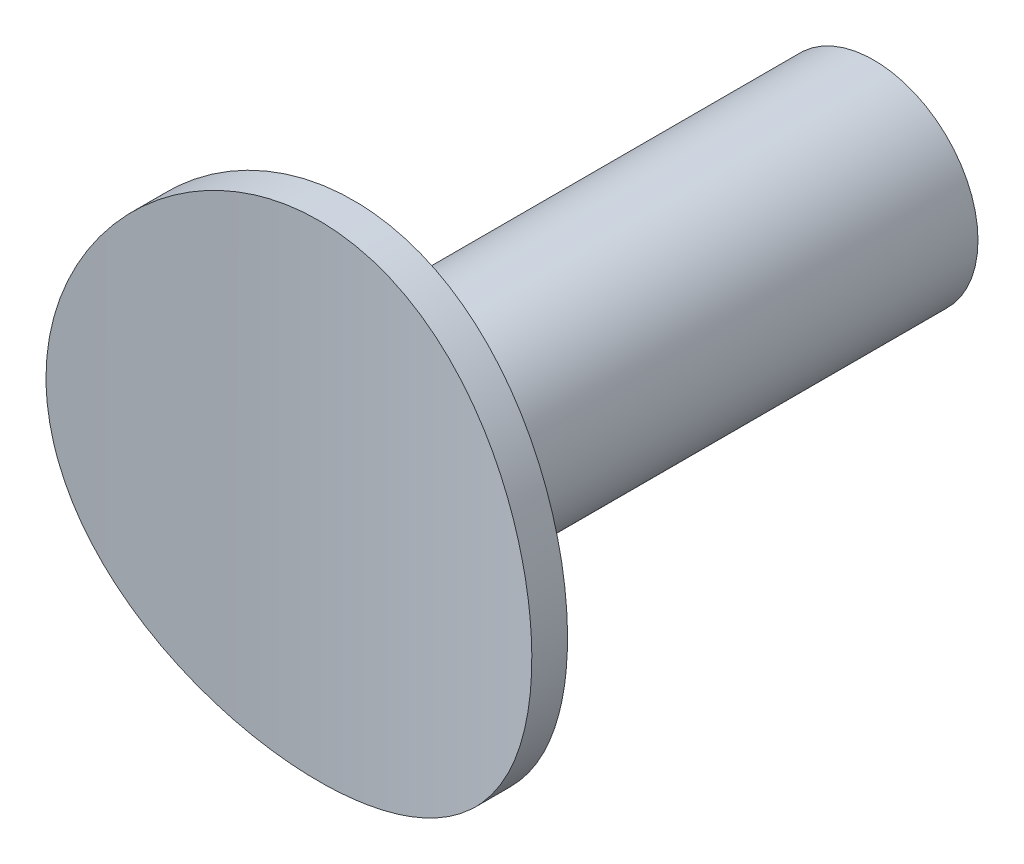
SolidWorks part; units mm, degrees
ref_plane "Front Plane" through (0, 0, 0) normal (0, 0, 1) x (1, 0, 0)
ref_plane "Top Plane" through (0, 0, 0) normal (0, 1, 0) x (1, 0, 0)
ref_plane "Right Plane" through (0, 0, 0) normal (1, 0, 0) x (0, 0, -1)
sketch "Curved Holder Main Body Sketch" plane through (0, 0, 0) normal (0, 0, 1) x (1, 0, 0)
  circle A0 centre (0, 0) radius 3.5
  dimension "D1" = 7
extrude "Curved Holder Main Body" add sketch "Curved Holder Main Body Sketch" along normal blind 5
sketch "Fill Remove Sketch" plane through (0, 0, 0) normal (0, 1, 0) x (1, 0, 0)
  line L13 (3.5, 0) -> (-3.5, 0) construction
  line L14 (3.5, -5) -> (3.5, 0) construction
  line L15 (-3.5, -5) -> (3.5, -5) construction
  line L16 (-3.5, 0) -> (-3.5, -5) construction
  line L17 (3.5, 0) -> (-3.5, 0) construction
  line L18 (3.5, -5) -> (3.5, -0.9288)
  line L19 (-3.5, -5) -> (3.5, -5)
  line L20 (-3.5, 0) -> (-3.5, -0.414)
  line L21 (-3.5, 0) -> (-3.5, 0.9782)
  line L22 (-3.5, 0.9782) -> (3.5, 0.9782)
  line L23 (3.5, 0.9782) -> (3.5, 0)
  line L24 (-3.5, -0.9288) -> (-3.5, -5)
  line L25 (3.5, -0.414) -> (3.5, 0)
  arc A2 (3.5, -0.414) -> (-3.5, -0.414) centre (0, -15) ccw
  arc A3 (3.5, -0.9288) -> (-3.5, -0.9288) centre (0, -15) ccw
  dimension "D2" = 29
  dimension "D3" = 0.5
extrude "Fill Remove" cut sketch "Fill Remove Sketch" against normal through all both and the other way through all
sketch "Pin Body Sketch" plane through (0, 0, 0) normal (0, 0, 1) x (1, 0, 0)
  circle A0 centre (0, 0) radius 1.5
  dimension "D1" = 3
extrude "Pin Body" add sketch "Pin Body Sketch" along normal up to next (0.5 mm away) and the other way blind 7.5
equation "\"mm\"=5"
